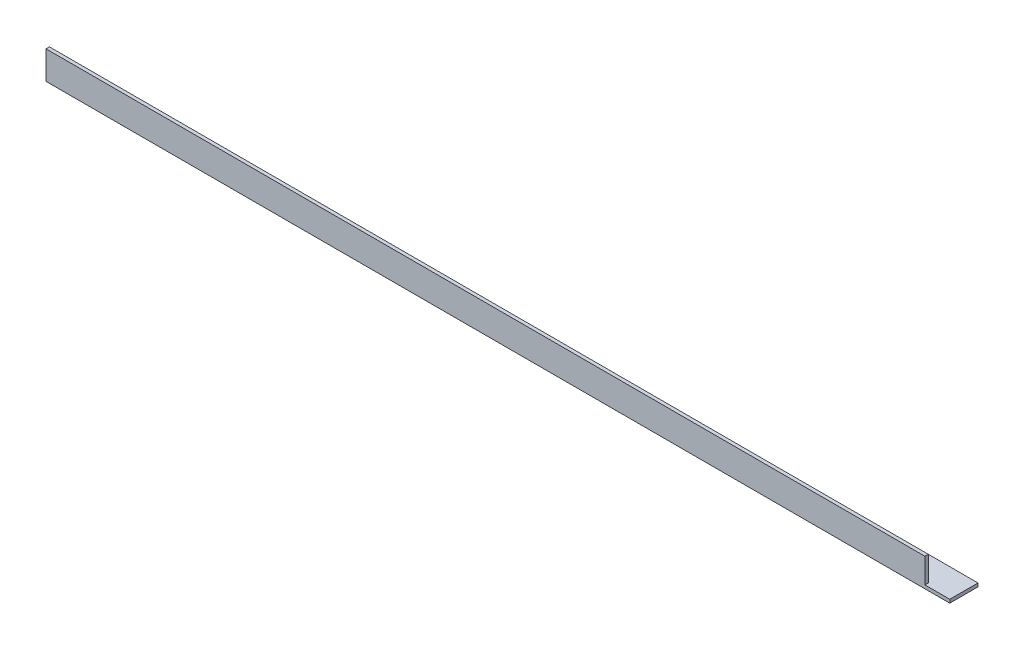
SolidWorks part; units mm, degrees
ref_plane "Спереди" through (0, 0, 0) normal (0, 0, 1) x (1, 0, 0)
ref_plane "Сверху" through (0, 0, 0) normal (0, 1, 0) x (1, 0, 0)
ref_plane "Справа" through (0, 0, 0) normal (1, 0, 0) x (0, 0, -1)
sketch "Эскиз1" plane through (0, 0, 0) normal (1, 0, 0) x (0, 0, -1)
  line L0 (0, 0) -> (25, 0)
  line L1 (0, 0) -> (0, 25)
extrude "Вытянуть-Тонкостенный1" add sketch "Эскиз1" along normal blind 800 thin thin type one direction wall 3
sketch "Эскиз2" plane through (0, 0, 0) normal (0, 0, 1) x (1, 0, 0)
  line L1 (800, 25) -> (778, 25)
  line L2 (800, 25) -> (800, 3)
  line L3 (800, 3) -> (778, 3)
  line L4 (778, 25) -> (778, 3)
extrude "Вырез-Вытянуть1" cut sketch "Эскиз2" against normal up to next
